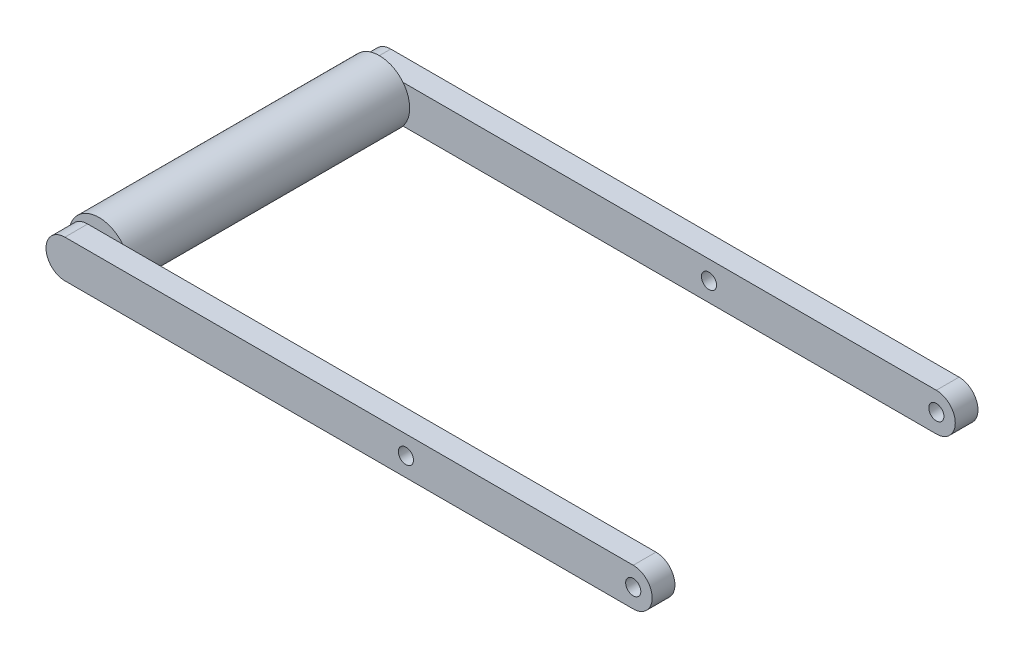
SolidWorks part; units mm, degrees
ref_plane "Front Plane" through (0, 0, 0) normal (0, 0, 1) x (1, 0, 0)
ref_plane "Top Plane" through (0, 0, 0) normal (0, 1, 0) x (1, 0, 0)
ref_plane "Right Plane" through (0, 0, 0) normal (1, 0, 0) x (0, 0, -1)
sketch "Sketch1" plane through (0, 0, 0) normal (0, 0, 1) x (1, 0, 0)
  line L1 (-400, 25) -> (400, 25)
  line L2 (-400, 25) -> (-400, -25)
  line L3 (-400, -25) -> (400, -25)
  line L4 (400, 25) -> (400, -25)
  line L5 (-400, 25) -> (400, -25) construction
  line L6 (-400, -25) -> (400, 25) construction
  point P0 (0, 0)
  dimension "D1" = 800
  dimension "D2" = 50
extrude "Boss-Extrude1" add sketch "Sketch1" along normal blind 30
sketch "Sketch2" plane through (0, 0, 30) normal (0, 0, 1) x (1, 0, 0)
  circle A0 centre (-360.0566, 0) radius 40
  point P2 (-360.0566, 0)
  dimension "D1" = 80
extrude "Boss-Extrude2" add sketch "Sketch2" along normal blind 370
ref_plane "Plane1" through (0, 0, 215) normal (0, 0, 1) x (1, 0, 0)
fillet "Fillet5" 2 edges at (400, 25, 15) (400, -25, 15) type full round first side face at (-120.0189, 25, 20) second side face at (-120.0189, -25, 20) middle face at (400, 0, 15)
fillet "Fillet6" 2 edges at (-400, 25, 15) (-400, -25, 15) type full round first side face at (-128.3522, 25, 20) second side face at (-128.3522, -25, 20) middle face at (-400, 0, 20)
mirror "Mirror3" about plane through (0, 0, 215) normal (0, 0, 1) of "Fillet6", "Fillet5", "Boss-Extrude1"
sketch "Sketch5" plane through (0, 0, 430) normal (0, 0, 1) x (1, 0, 0)
  circle A0 centre (75, 0) radius 10
  arc A1 (375, -25) -> (375, 25) centre (375, 0) ccw construction
  dimension "D1" = 20
  dimension "D2" = 300
extrude "Cut-Extrude3" cut sketch "Sketch5" against normal through all and the other way through all
sketch "Sketch6" plane through (0, 0, 430) normal (0, 0, 1) x (1, 0, 0)
  circle A0 centre (375, 0) radius 10
  dimension "D1" = 20
extrude "Cut-Extrude4" cut sketch "Sketch6" against normal through all
